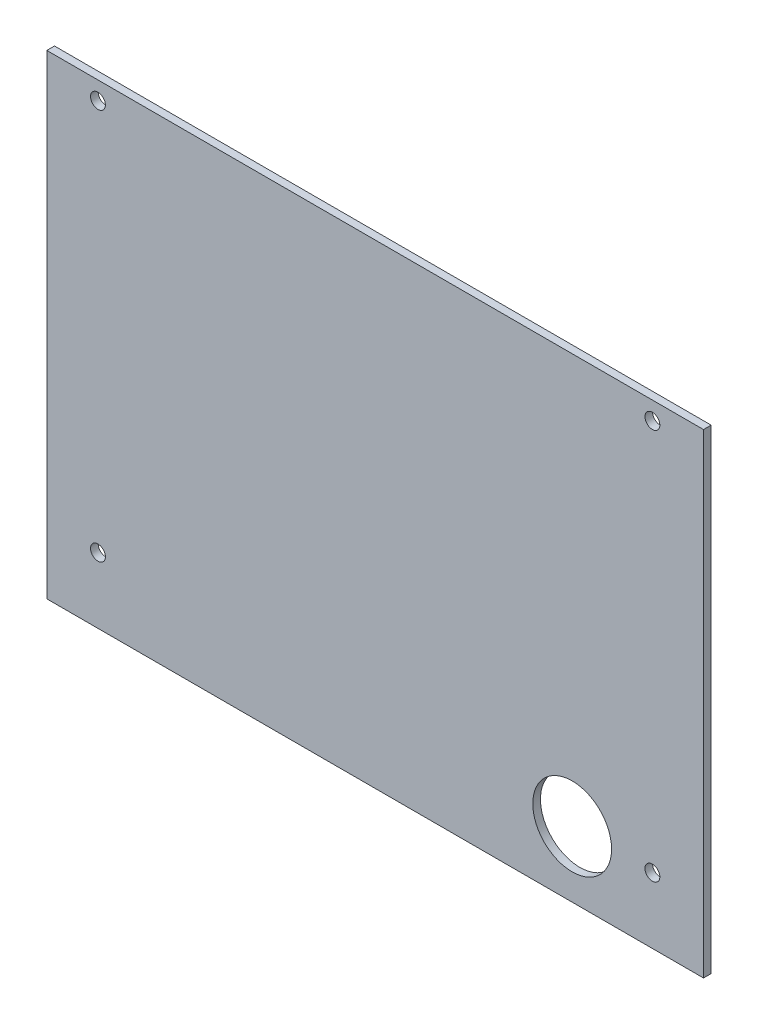
SolidWorks part; units mm, degrees
note: The reader was unsure of these and kept them because the rebuilt part matched: thickness of "Base-Flange1", "Sheet-Metal1", "Sheet-Metal2", "Sheet-Metal5", "Sheet-Metal6".
ref_plane "Front Plane" through (0, 0, 0) normal (0, 0, 1) x (1, 0, 0)
ref_plane "Top Plane" through (0, 0, 0) normal (0, 1, 0) x (1, 0, 0)
ref_plane "Right Plane" through (0, 0, 0) normal (1, 0, 0) x (0, 0, -1)
sketch "Sketch1" plane through (0, 0, 0) normal (0, 0, 1) x (1, 0, 0)
  line L0 (64.825, 101.7741) -> (-64.825, 101.7741) construction
  line L1 (-75, 101.7741) -> (75, 101.7741)
  line L2 (-75, 101.7741) -> (-75, -6.7259)
  line L3 (-75, -6.7259) -> (75, -6.7259)
  line L4 (75, 101.7741) -> (75, -6.7259)
  line L5 (75, -6.7259) -> (-75, -6.7259) construction
  point P0 (0, 0)
  dimension "D1" = 150
base flange "Base-Flange1" sketch "Sketch1" thickness 1.75 reverse thickness direction no parameters "D1"=3.048
sketch "Sketch6" plane through (0, 0, 0) normal (0, 0, 1) x (1, 0, 0)
  line L0 (75, 8.2741) -> (45, 8.2741) construction
  line L1 (75, -6.7259) -> (75, 101.7741) construction
  line L2 (45, 8.2741) -> (45, -6.7259) construction
  line L3 (-75, -6.7259) -> (75, -6.7259) construction
  circle A0 centre (45, 8.2741) radius 9
  dimension "D3" = 18
  dimension "D1" = 30
  dimension "D2" = 15
extrude "Cut-Extrude1" cut sketch "Sketch6" against normal up to next normal cut yes
hole_wizard "M3 Clearance Hole1" positions "Sketch10" profile "Sketch11" hole size "M3" standard "ANSI Metric" end condition up to next
sketch "Sketch10" plane through (0, 0, 0) normal (0, 0, 1) x (1, 0, 0)
  point P0 (63.325, 8.2741)
  point P7 (63.325, 97.6491)
  point P10 (0, 0)
sketch "Sketch11" plane through (63.325, 8.2741, 0) normal (1, 0, 0) x (0, -1, 0)
  line L0 (0, 0) -> (0, 1.75)
  line L1 (0, 1.75) -> (1.7, 1.75)
  line L2 (1.7, 1.75) -> (1.7, 0)
  line L5 (1.7, 0) -> (0, 0)
  line L11 (0, -6.35) -> (0, 107.95) construction
  dimension "Thru Hole Dia." = 3.4
  dimension "Thru Hole Depth" = 1.75
mirror "Mirror1" about plane through (0, 0, 0) normal (1, 0, 0) of "M3 Clearance Hole1"
sketch "Bend-Lines1" [suppressed] plane through (0, 0, 0) normal (0, 1, 0) x (1, 0, 0)
sketch "Bounding-Box1" [suppressed] plane through (0, 0, 0) normal (0, 1, 0) x (1, 0, 0)
sheet metal parameters "Sheet-Metal1" thickness 1.75 parameters "D1"=3.048, "D7"=1.016
flat pattern "Flat-Pattern1" [suppressed]
sketch "Bend-Lines2" plane through (0, 0, 0) normal (0, 1, 0) x (1, 0, 0)
sketch3d "Bounding-Box2" [suppressed]
  line L0 (-75, -1.8258, 0) -> (75, -1.8258, 0) construction
  line L1 (-75, 134.0842, 0) -> (75, 134.0842, 0) construction
  line L2 (-75, -1.8258, 0) -> (-75, 134.0842, 0) construction
  line L3 (75, -1.8258, 0) -> (75, 134.0842, 0) construction
sheet metal parameters "Sheet-Metal2" thickness 1.75 parameters "D1"=3.048, "D7"=1.016
flat pattern "Flat-Pattern1"
sketch "Bend-Lines2" plane through (0, 0, 0) normal (0, 1, 0) x (1, 0, 0)
sketch3d "Bounding-Box2" [suppressed]
  line L0 (-75, -6.7259, 0) -> (75, -6.7259, 0) construction
  line L1 (-75, 128.1681, 0) -> (75, 128.1681, 0) construction
  line L2 (-75, -6.7259, 0) -> (-75, 128.1681, 0) construction
  line L3 (75, -6.7259, 0) -> (75, 128.1681, 0) construction
sheet metal parameters "Sheet-Metal5" thickness 1.75 parameters "D1"=3.048, "D7"=1.016
flat pattern "Flat-Pattern1"
sketch "Bend-Lines2" plane through (0, 0, 0) normal (0, 1, 0) x (1, 0, 0)
sketch3d "Bounding-Box2" [suppressed]
  line L0 (-75, -6.7259, 0) -> (75, -6.7259, 0) construction
  line L1 (-75, 128.1681, 0) -> (75, 128.1681, 0) construction
  line L2 (-75, -6.7259, 0) -> (-75, 128.1681, 0) construction
  line L3 (75, -6.7259, 0) -> (75, 128.1681, 0) construction
sheet metal parameters "Sheet-Metal6" thickness 1.75 parameters "D1"=3.048, "D7"=1.016
flat pattern "Flat-Pattern1"
sketch "Bend-Lines2" plane through (0, 0, 0) normal (0, 1, 0) x (1, 0, 0)
sketch3d "Bounding-Box2" [suppressed]
  line L0 (-75, -6.7259, 0) -> (75, -6.7259, 0) construction
  line L1 (-75, 101.7741, 0) -> (75, 101.7741, 0) construction
  line L2 (-75, -6.7259, 0) -> (-75, 101.7741, 0) construction
  line L3 (75, -6.7259, 0) -> (75, 101.7741, 0) construction
